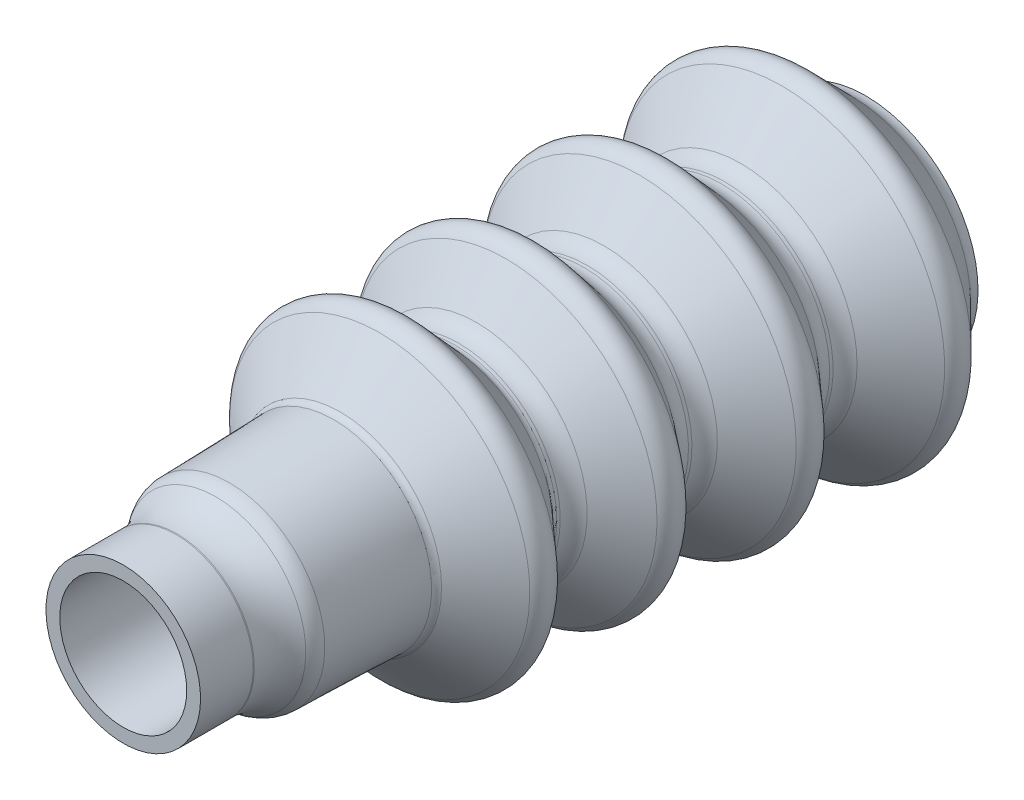
SolidWorks part; units mm, degrees
material "Rubber"
ref_plane "Front Plane" through (0, 0, 0) normal (0, 0, 1) x (1, 0, 0)
ref_plane "Top Plane" through (0, 0, 0) normal (0, 1, 0) x (1, 0, 0)
ref_plane "Right Plane" through (0, 0, 0) normal (1, 0, 0) x (0, 0, -1)
sketch "Sketch20" plane through (0, 0, 0) normal (1, 0, 0) x (0, 0, -1)
  line L0 (-152.3388, 13.9342) -> (-152.7166, 13.9241)
  line L1 (-284.8495, 8.7) -> (-284.8495, 3.2367)
  line L2 (-235.0438, 12.7218) -> (-238.6007, 17.0873)
  line L3 (0, 0) -> (-524.5166, 0) construction
  line L4 (-274.1018, 23.1803) -> (-149.8664, 26.487) construction
  line L5 (-154.6462, 14.7358) -> (-159.1107, 19.5481)
  line L6 (-162.1134, 19.4682) -> (-166.3156, 14.4252)
  line L7 (-170.4685, 14.2732) -> (-175.2673, 19.2237)
  line L8 (-178.2114, 19.1453) -> (-182.74, 13.9466)
  line L9 (-186.8831, 13.8646) -> (-191.4517, 18.7212)
  line L10 (-194.436, 18.6418) -> (-198.7397, 13.549)
  line L11 (-202.8704, 13.3993) -> (-207.7658, 18.3874)
  line L12 (-210.6931, 18.3095) -> (-215.3162, 13.068)
  line L13 (-219.4895, 13.0418) -> (-223.7091, 17.7447)
  line L14 (-226.7553, 17.6636) -> (-230.7187, 12.7429)
  line L16 (-139.8495, 26.487) -> (-139.8495, 0)
  line L17 (-139.8495, 0) -> (-274.8495, 0)
  line L18 (-241.7667, 17.003) -> (-245.0863, 12.4545)
  line L19 (-248.2176, 11.7329) -> (-252.9447, 16.978)
  line L20 (-255.9852, 16.897) -> (-260.4266, 11.4079)
  line L21 (-139.8495, 26.487) -> (-142.2464, 26.487)
  line L22 (-149.8664, 18.867) -> (-149.8664, 16.4733)
  line L23 (-168.1994, 13.512) -> (-168.5772, 13.502)
  line L24 (-184.5877, 13.0758) -> (-184.9654, 13.0658)
  line L25 (-200.6122, 12.6493) -> (-200.99, 12.6393)
  line L26 (-217.1536, 12.209) -> (-217.5313, 12.199)
  line L27 (-232.6293, 11.7971) -> (-233.0071, 11.7871)
  line L28 (-247.0704, 11.4128) -> (-247.4482, 11.4027)
  line L29 (-261.1774, 11.0373) -> (-272.8874, 10.7256)
  line L32 (-278.919, 8.7) -> (-284.8495, 8.7)
  line L33 (-284.8495, 3.2367) -> (-274.8495, 3.2367)
  line L34 (-274.8495, 3.2367) -> (-274.8495, 0)
  line L35 (-139.8495, 26.487) -> (-139.8495, 22.405) construction
  arc A0 (-159.1107, 19.5481) -> (-162.1134, 19.4682) centre (-160.5769, 18.1879) ccw
  arc A1 (-175.2673, 19.2237) -> (-178.2114, 19.1453) centre (-176.7033, 17.8316) ccw
  arc A2 (-191.4517, 18.7212) -> (-194.436, 18.6418) centre (-192.9084, 17.3509) ccw
  arc A3 (-207.7658, 18.3874) -> (-210.6931, 18.3095) centre (-209.1932, 16.9865) ccw
  arc A4 (-223.7091, 17.7447) -> (-226.7553, 17.6636) centre (-225.1977, 16.4091) ccw
  arc A5 (-238.6007, 17.0873) -> (-241.7667, 17.003) centre (-240.1512, 15.824) ccw
  arc A6 (-252.9447, 16.978) -> (-255.9852, 16.897) centre (-254.4304, 15.639) ccw
  arc A7 (-260.4266, 11.4079) -> (-261.1774, 11.0373) centre (-261.204, 12.0369) cw
  arc A8 (-248.2176, 11.7329) -> (-247.4482, 11.4027) centre (-247.4748, 12.4024) ccw
  arc A9 (-274.4406, 10.1422) -> (-278.7909, 8.6968) centre (-278.4721, 15.0065) cw
  arc A10 (-149.8664, 16.4733) -> (-152.3388, 13.9342) centre (-152.4064, 16.4733) cw
  arc A11 (-154.6462, 14.7358) -> (-152.7166, 13.9241) centre (-152.7841, 16.4632) ccw
  arc A12 (-166.3156, 14.4252) -> (-168.1994, 13.512) centre (-168.2669, 16.0511) cw
  arc A13 (-170.4685, 14.2732) -> (-168.5772, 13.502) centre (-168.6447, 16.0411) ccw
  arc A14 (-182.74, 13.9466) -> (-184.5877, 13.0758) centre (-184.6552, 15.6149) cw
  arc A15 (-186.8831, 13.8646) -> (-184.9654, 13.0658) centre (-185.033, 15.6049) ccw
  arc A16 (-198.7397, 13.549) -> (-200.6122, 12.6493) centre (-200.6798, 15.1884) cw
  arc A17 (-202.8704, 13.3993) -> (-200.99, 12.6393) centre (-201.0576, 15.1784) ccw
  arc A18 (-215.3162, 13.068) -> (-217.1536, 12.209) centre (-217.2211, 14.7481) cw
  arc A19 (-219.4895, 13.0418) -> (-217.5313, 12.199) centre (-217.5989, 14.7381) ccw
  arc A20 (-230.7187, 12.7429) -> (-232.6293, 11.7971) centre (-232.6969, 14.3362) cw
  arc A21 (-235.0438, 12.7218) -> (-233.0071, 11.7871) centre (-233.0747, 14.3262) ccw
  arc A22 (-245.0863, 12.4545) -> (-247.0704, 11.4128) centre (-247.138, 13.9519) cw
  arc A23 (-274.4406, 10.1422) -> (-272.8874, 10.7256) centre (-272.8198, 8.1865) cw
  arc A24 (-278.919, 8.7) -> (-278.7909, 8.6968) centre (-278.919, 6.16) cw
  arc A25 (-142.2464, 26.487) -> (-149.8664, 18.867) centre (-142.2464, 18.867) ccw
  arc A26 (-200.6122, 12.6493) -> (-207.3495, 0) centre (-200.9244, 4.6967) ccw
  point P27 (-149.8664, 14)
  point P36 (-160.6575, 21.2154)
  point P39 (-176.782, 20.7863)
  point P42 (-192.9884, 20.3549)
  point P45 (-209.2713, 19.9215)
  point P48 (-225.2799, 19.4954)
  point P51 (-240.2383, 19.0973)
  point P54 (-254.5123, 18.7173)
  point P57 (-260.7165, 11.0496)
  point P60 (-247.909, 11.3904)
  point P64 (-153.8649, 13.8936)
  point P73 (-167.051, 13.5426)
  point P76 (-169.6922, 13.4723)
  point P79 (-183.4726, 13.1055)
  point P82 (-186.1033, 13.0355)
  point P85 (-199.4744, 12.6796)
  point P88 (-202.0957, 12.6098)
  point P91 (-216.0479, 12.2385)
  point P94 (-218.7053, 12.1677)
  point P97 (-231.4554, 11.8284)
  point P100 (-234.2552, 11.7539)
  point P103 (-245.8223, 11.446)
  dimension "D4" = 2
  dimension "D5" = 1
  dimension "D2" = 2.54
  dimension "D3" = 7.62
  dimension "D10" = 4
ref_axis "Axis5" through (0, 0, 136.4745) along (0, 0, 1)
revolve "Revolve5" add sketch "Sketch20" angle 360 about L17 region at (0, 7.3988, 240.8708)
sketch "Sketch21" plane through (0, 0, 284.8495) normal (0, 0, 1) x (1, 0, 0)
  circle A0 centre (0, 0) radius 7.1438
  dimension "D1" = 14.2875
extrude "Cut-Extrude1" cut sketch "Sketch21" against normal through all
